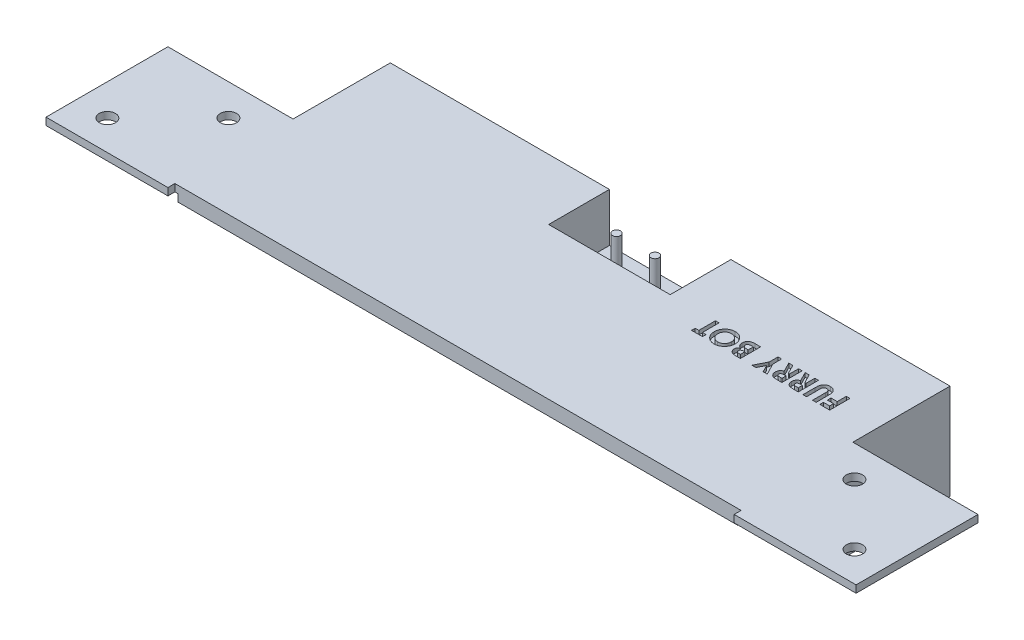
SolidWorks part; units mm, degrees
ref_plane "Alzado" through (0, 0, 0) normal (0, 0, 1) x (1, 0, 0)
ref_plane "Planta" through (0, 0, 0) normal (0, 1, 0) x (1, 0, 0)
ref_plane "Vista lateral" through (0, 0, 0) normal (1, 0, 0) x (0, 0, -1)
sketch "Croquis1" plane through (0, 0, 0) normal (0, 1, 0) x (1, 0, 0)
  line L0 (0, 16.8548) -> (0, -58.7896) construction
  line L1 (-69.5, -36.2916) -> (-69.5, -34.5716) construction
  line L2 (-100, -36.2916) -> (-69.5, -36.2916) construction
  line L3 (-100, -5.7916) -> (-100, -36.2916) construction
  line L4 (-69.5, -5.7916) -> (-100, -5.7916) construction
  line L5 (-69.5, -34.5716) -> (-69.5, -5.7916) construction
  line L17 (-69.5, -9.7916) -> (69.5, -9.7916) construction
  line L18 (69.5, -34.5716) -> (69.5, -5.7916) construction
  line L19 (69.5, -5.7916) -> (100, -5.7916) construction
  line L20 (100, -5.7916) -> (100, -36.2916) construction
  line L21 (100, -36.2916) -> (69.5, -36.2916) construction
  line L22 (69.5, -36.2916) -> (69.5, -34.5716) construction
  line L23 (69.5, -34.5716) -> (-69.5, -34.5716) construction
  circle A0 centre (-77.2782, -13.5698) radius 2 construction
  circle A1 centre (-92.2218, -28.5135) radius 2 construction
  circle A2 centre (-56.5, -26.2016) radius 2 construction
  circle A11 centre (56.5, -26.2016) radius 2 construction
  circle A12 centre (92.2218, -28.5135) radius 2 construction
  circle A13 centre (77.2782, -13.5698) radius 2 construction
  point P23 (0, -34.5716)
  point P28 (0, -9.7916)
sketch "Croquis4" plane through (0, 0, 0) normal (0, 1, 0) x (1, 0, 0)
  line L0 (69.5, -34.5716) -> (-69.5, -34.5716) construction
  line L1 (100, -36.2916) -> (69.5, -36.2916) construction
  line L2 (100, -5.7916) -> (100, -36.2916) construction
  line L3 (69.5, -5.7916) -> (100, -5.7916) construction
  line L5 (-69.5, -9.7916) -> (69.5, -9.7916) construction
  line L6 (0, 16.8548) -> (0, -58.7896) construction
  line L7 (69.5, -34.5716) -> (0, -34.5716) construction
  line L8 (100, -36.2916) -> (69.5, -36.2916) construction
  line L9 (100, -5.7916) -> (100, -36.2916) construction
  line L10 (69.5, -5.7916) -> (100, -5.7916) construction
  line L12 (0, -9.7916) -> (69.5, -9.7916) construction
  line L13 (0, 16.8548) -> (0, -58.7896) construction
  line L15 (69.5, -36.2916) -> (69.5, -34.5716) construction
  line L16 (69.5, -36.2916) -> (69.5, -34.5716) construction
  line L17 (100, -35.8916) -> (69.9, -35.8916)
  line L18 (69.9, -35.8916) -> (69.9, -34.1716)
  line L19 (69.9, -34.1716) -> (0, -34.1716)
  line L20 (100, -35.8916) -> (100, -5.7916)
  line L22 (100, -5.7916) -> (-100, -5.7916)
  line L23 (-69.9, -34.1716) -> (0, -34.1716)
  line L24 (-69.9, -35.8916) -> (-69.9, -34.1716)
  line L25 (-100, -35.8916) -> (-69.9, -35.8916)
  line L26 (-100, -35.8916) -> (-100, -5.7916)
  point P21 (0, -5.7916)
  dimension "D1" = 0.4
extrude "Saliente-Extruir1" add sketch "Croquis4" along normal blind 1.8
sketch "Croquis5" plane through (0, 1.8, 0) normal (0, 1, 0) x (1, 0, 0)
  line L0 (69.5, -34.5716) -> (-69.5, -34.5716) construction
  line L1 (69.5, -34.5716) -> (69.5, -5.7916) construction
  line L2 (-69.5, -9.7916) -> (69.5, -9.7916) construction
  line L3 (0, 16.8548) -> (0, -58.7896) construction
  line L4 (69.5, -34.5716) -> (0, -34.5716) construction
  line L5 (69.5, -34.5716) -> (69.5, -9.7916) construction
  line L6 (0, -9.7916) -> (69.5, -9.7916) construction
  line L7 (0, 16.8548) -> (0, -58.7896) construction
  line L11 (-69.1, -34.1716) -> (69.1, -34.1716)
  line L17 (-69.9, -34.1716) -> (69.9, -34.1716) construction
  line L18 (69.1, -34.1716) -> (69.1, -9.7916)
  line L19 (69.1, -34.5716) -> (69.1, -9.7916) construction
  line L20 (69.1, -9.7916) -> (69.1, -5.7916)
  line L21 (100, -5.7916) -> (-100, -5.7916) construction
  line L22 (69.1, -5.7916) -> (-69.1, -5.7916)
  line L23 (-69.1, -34.1716) -> (-69.1, -9.7916)
  line L24 (-69.1, -9.7916) -> (-69.1, -5.7916)
  point P20 (0, -10.2916)
  point P21 (0, -34.1716)
  point P23 (0, -5.7916)
  dimension "D1" = 0.4
extrude "Saliente-Extruir2" add sketch "Croquis5" against normal blind 1.8 from surface starting at face at (0, 0, 27.9366)
sketch "Croquis6" plane through (0, 1.8, 0) normal (0, 1, 0) x (1, 0, 0)
  line L0 (-69.5, -9.7916) -> (69.5, -9.7916) construction
  line L1 (0, -9.7916) -> (69.5, -9.7916) construction
  line L2 (0, 16.8548) -> (0, -58.7896) construction
  line L3 (0, 16.8548) -> (0, -58.7896) construction
  line L4 (69.5, -34.5716) -> (69.5, -5.7916) construction
  line L5 (69.5, -9.7916) -> (69.5, -5.7916) construction
  line L14 (-69.1, -9.1916) -> (69.1, -9.1916)
  line L15 (69.1, -9.1916) -> (69.1, -5.7916)
  line L16 (69.1, -9.7916) -> (69.1, -5.7916) construction
  line L17 (0, -9.1916) -> (69.5, -9.1916) construction
  line L18 (69.1, -5.7916) -> (-69.1, -5.7916)
  line L19 (100, -5.7916) -> (-100, -5.7916) construction
  line L20 (-69.1, -9.1916) -> (-69.1, -5.7916)
  point P17 (0, -5.7916)
  dimension "D1" = 0.6
  dimension "D2" = 0.4
extrude "Saliente-Extruir3" add sketch "Croquis6" against normal blind 20 from surface starting at face at (0, -1.8, 19.9816)
sketch "Croquis7" plane through (0, 0, 5.7916) normal (0, 0, -1) x (-1, 0, 0)
  line L0 (0, 22.365) -> (0, -38.5622) construction
  line L1 (0, 1.8) -> (75, 1.8)
  line L2 (-100, 1.8) -> (100, 1.8) construction
  line L3 (75, 1.8) -> (75, -21.8)
  line L4 (-69.1, -21.8) -> (69.1, -21.8) construction
  line L5 (75, -21.8) -> (0, -21.8)
  dimension "D1" = 75
sketch "Croquis8" plane through (0, 0, 5.7916) normal (0, 0, -1) x (-1, 0, 0)
  line L0 (0, 22.365) -> (0, -38.5622) construction
  line L1 (0, 22.365) -> (0, -38.5622) construction
  line L2 (-69.1, 1.8) -> (69.1, 1.8)
  line L3 (0, 1.8) -> (75, 1.8) construction
  line L4 (69.1, 1.8) -> (69.1, -21.8)
  line L5 (69.1, -21.8) -> (-69.1, -21.8)
  line L6 (-69.1, 1.8) -> (-69.1, -21.8)
  point P12 (0, 1.8)
  point P13 (0, -21.8)
extrude "Saliente-Extruir4" add sketch "Croquis8" along normal blind 24
sketch "Croquis9" plane through (0, 1.8, 0) normal (0, 1, 0) x (1, 0, 0)
  line L0 (0, 16.8548) -> (0, -58.7896) construction
  line L1 (0, 33.1742) -> (0, -58.7896) construction
  line L2 (15, 18.2084) -> (-15, 18.2084)
  line L3 (-69.1, 18.2084) -> (69.1, 18.2084) construction
  line L4 (-15, 18.2084) -> (-15, 3.2084)
  line L5 (-15, 3.2084) -> (15, 3.2084)
  line L6 (15, 18.2084) -> (15, 3.2084)
  point P10 (0, 3.2084)
  point P11 (0, 18.2084)
  dimension "D1" = 15
  dimension "D2" = 15
extrude "Cortar-Extruir1" cut sketch "Croquis9" against normal blind 12
sketch "Croquis10" plane through (0, -10.2, 0) normal (0, 1, 0) x (1, 0, 0)
  line L0 (0, 16.8548) -> (0, -58.7896) construction
  line L1 (0, 22.5663) -> (0, -58.7896) construction
  line L2 (15, 18.2084) -> (-15, 18.2084) construction
  line L3 (15, 18.2084) -> (-15, 18.2084) construction
  circle A0 centre (-4.75, 9.7084) radius 1
  circle A1 centre (4.75, 9.7084) radius 1
  dimension "D1" = 2
  dimension "D2" = 4.75
  dimension "D3" = 8.5
extrude "Saliente-Extruir5" add sketch "Croquis10" along normal up to surface (12 mm away) up to face at (0, 1.8, 9.7391)
sketch "Croquis11" plane through (0, 1.8, 0) normal (0, 1, 0) x (1, 0, 0)
  circle A0 centre (92.2218, -28.5135) radius 2 construction
  circle A1 centre (77.2782, -13.5698) radius 2 construction
  circle A2 centre (-77.2782, -13.5698) radius 2 construction
  circle A3 centre (-92.2218, -28.5135) radius 2 construction
  circle A4 centre (92.2218, -28.5135) radius 2
  circle A5 centre (77.2782, -13.5698) radius 2
  circle A6 centre (-77.2782, -13.5698) radius 2
  circle A7 centre (-92.2218, -28.5135) radius 2
extrude "Cortar-Extruir2" cut sketch "Croquis11" against normal through all
sketch "Croquis12" plane through (0, 1.8, 0) normal (0, 1, 0) x (1, 0, 0)
  line L0 (23.4463, 3.2084) -> (61.6634, 3.2084) construction
  text T0 "FURRY BOT" font "Century Gothic" height 5
extrude "Cortar-Extruir4" cut sketch "Croquis12" against normal blind 1
